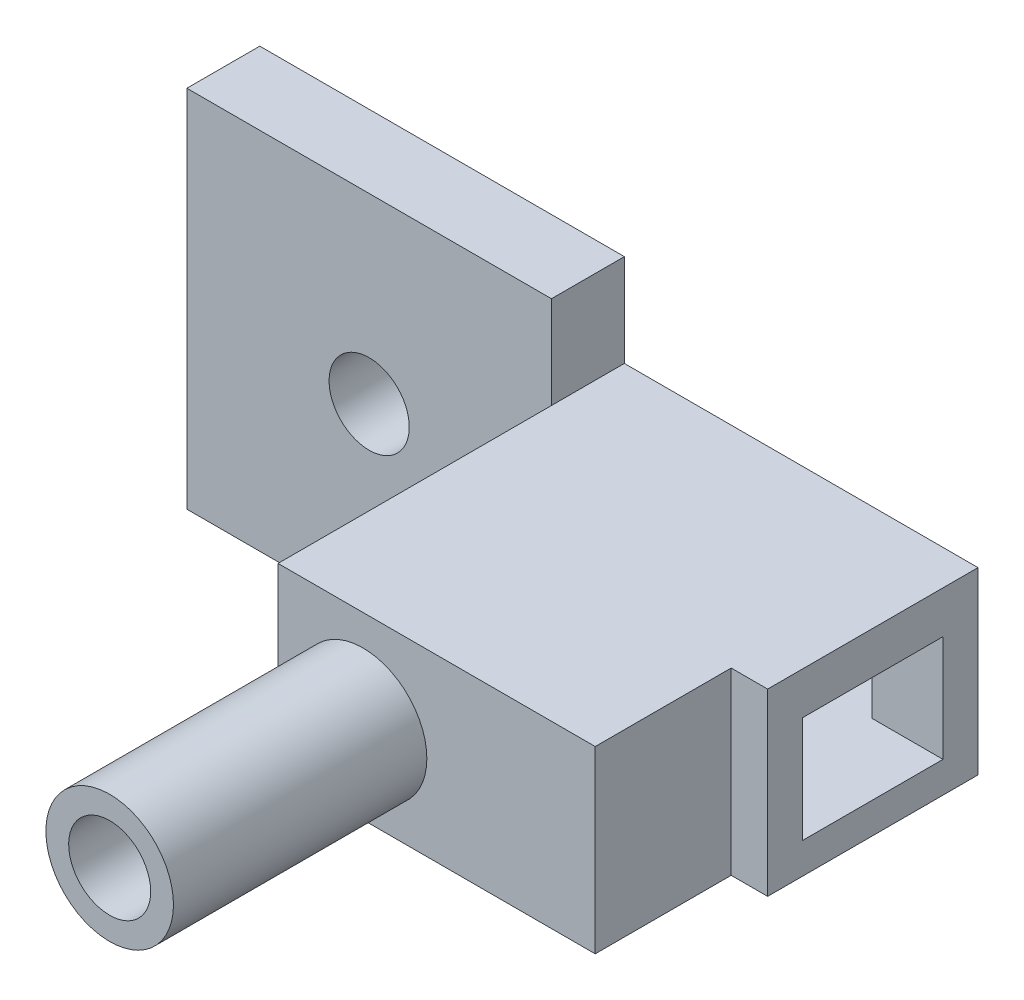
SolidWorks part; units mm, degrees
ref_plane "Front Plane" through (0, 0, 0) normal (0, 0, 1) x (1, 0, 0)
ref_plane "Top Plane" through (0, 0, 0) normal (0, 1, 0) x (1, 0, 0)
ref_plane "Right Plane" through (0, 0, 0) normal (1, 0, 0) x (0, 0, -1)
sketch "Sketch1" plane through (0, 0, 0) normal (0, 0, 1) x (1, 0, 0)
  line L0 (3.92, 6.85) -> (1.72, 6.85) construction
  line L1 (-2, 7.85) -> (15.4, 7.85)
  line L2 (-2, 7.85) -> (-2, -2.0005)
  line L3 (-2, -2.0005) -> (15.4, -2.0005)
  line L4 (15.4, 7.85) -> (15.4, -2.0005)
  line L5 (13.4, 0) -> (0, 0) construction
  line L6 (0, 0) -> (0, 5.33) construction
  line L7 (13.4, 5.33) -> (13.4, 0) construction
  line L8 (0, 4.9339) -> (0, 0.3961)
  line L9 (0.3961, 5.33) -> (4.9339, 5.33)
  line L10 (0, 5.33) -> (13.4, 5.33) construction
  line L11 (0.3961, 0) -> (4.9339, 0)
  circle A0 centre (2.665, 2.665) radius 2.25
  circle A2 centre (2.665, 2.665) radius 3.5
  dimension "D1" = 4.5
  dimension "D2" = 7
  dimension "D3" = 1
  dimension "D4" = 2.0005
  dimension "D5" = 2
  dimension "D6" = 2
extrude "Boss-Extrude1" add sketch "Sketch1" along normal blind 2 contours L8 A2 | L11 A2 | L9 A2 | L4 L1 L2 L3 A2 A0 region at (7.8683, 3, 0) region at (-0.3377, 2.665, 0) region at (2.665, 5.6677, 0) region at (2.665, -0.3377, 0)
extrude "Boss-Extrude2" add sketch "Sketch1<4>" along normal blind 14 from offset 1.9 contours L9 A2 L8 L11 A0 | L8 A2 | L9 A2 | L11 A2 region at (0.2478, 5.0822, 0) region at (-0.3377, 2.665, 0) region at (2.665, 5.6677, 0) region at (2.665, -0.3377, 0)
sketch "Sketch1<4>" plane through (0, 0, 0) normal (0, 0, 1) x (1, 0, 0) same geometry as "Sketch1"
sketch "Sketch2" plane through (0, 0, 0) normal (0, 0, -1) x (-1, 0, 0)
  line L0 (-13.5, 5.53) -> (-11.88, 5.53)
  line L1 (-13.5, -0.3) -> (0.1, -0.3)
  line L2 (-13.5, -0.3) -> (-13.5, 5.53)
  line L4 (0.1, -0.3) -> (0.1, 5.63)
  line L5 (-11.88, 5.53) -> (-11.88, 7.05)
  line L6 (-11.88, 7.05) -> (-9.28, 7.05)
  line L7 (-9.28, 7.05) -> (-9.28, 5.63)
  line L8 (-9.28, 5.63) -> (-4.12, 5.63)
  line L9 (-4.12, 5.63) -> (-4.12, 7.05)
  line L10 (-4.12, 7.05) -> (-1.52, 7.05)
  line L11 (-1.52, 7.05) -> (-1.52, 5.63)
  line L12 (-1.52, 5.63) -> (0.1, 5.63)
  line L13 (-13.4, 5.33) -> (-13.4, 0) construction
  line L15 (-13.4, 0) -> (0, 0) construction
  line L17 (0, 4.9339) -> (0, 0.3961) construction
  line L19 (0, 5.33) -> (-13.4, 5.33) construction
  line L21 (-9.48, 6.85) -> (-11.68, 6.85) construction
  line L22 (-11.68, 6.85) -> (-11.68, 5.33) construction
  line L23 (-1.72, 5.33) -> (-1.72, 6.85) construction
  line L26 (-1.72, 6.85) -> (-3.92, 6.85) construction
  line L27 (-3.92, 6.85) -> (-3.92, 5.33) construction
  line L28 (-9.48, 5.33) -> (-9.48, 6.85) construction
  line L30 (-15.4, 7.85) -> (2, 7.85)
  line L31 (-15.4, 7.85) -> (-15.4, -2.0005)
  line L32 (-15.4, -2.0005) -> (2, -2.0005)
  line L33 (2, 7.85) -> (2, -2.0005)
  dimension "D1" = 0.1
  dimension "D2" = 0.3
  dimension "D3" = 0.1
  dimension "D4" = 0.3
  dimension "D5" = 0.2
  dimension "D6" = 0.2
  dimension "D7" = 0.2
  dimension "D8" = 0.2
  dimension "D9" = 0.2
  dimension "D10" = 0.2
  dimension "D11" = 0.2
extrude "Boss-Extrude3" add sketch "Sketch2" along normal blind 17
sketch "Sketch4" plane through (13.5, 0, 0) normal (-1, 0, 0) x (0, 0, 1)
  line L0 (-17, -0.3) -> (0, -0.3) construction
  line L1 (-15.08, 5.53) -> (-7.38, 5.53)
  line L2 (-15.08, 5.53) -> (-15.08, -0.3)
  line L3 (-15.08, -0.3) -> (-7.38, -0.3)
  line L4 (-7.38, 5.53) -> (-7.38, -0.3)
  line L5 (-17, 5.53) -> (0, 5.53) construction
  line L6 (-6.88, 5.33) -> (-6.88, 0) construction
  dimension "D1" = 7.7
  dimension "D2" = 0.5
extrude "Cut-Extrude1" cut sketch "Sketch4" against normal up to surface (1.9 mm away) up to face at (15.4, 2.9248, -7.5)
sketch "Sketch5" plane through (0, 0, -17) normal (0, 0, -1) x (-1, 0, 0)
  line L0 (2, -2.0005) -> (2, 7.85) construction
  line L1 (2, 12.9248) -> (22, 12.9248)
  line L2 (2, 12.9248) -> (2, -7.0752)
  line L3 (2, -7.0752) -> (22, -7.0752)
  line L4 (22, 12.9248) -> (22, -7.0752)
  line L5 (2, -7.0752) -> (22, 12.9248) construction
  circle A0 centre (12, 2.9248) radius 2.2
  point P6 (2, 2.9248)
  point P7 (2, 2.9248)
  point P11 (12, 2.9248)
  dimension "D3" = 4.4
  dimension "D1" = 20
  dimension "D2" = 20
extrude "Boss-Extrude4" add sketch "Sketch5" against normal blind 4
chamfer "Chamfer1" distance 0.5 angle 45 6 edges at (0.1901, 5.1399, 1.9) (0, 2.665, 1.9) (0.1901, 0.1901, 1.9) (2.665, 0, 1.9) (6.165, 2.665, 1.9) (2.665, 5.33, 1.9)
sketch "Sketch6" plane through (15.4, 0, 0) normal (1, 0, 0) x (0, 0, -1)
  line L0 (-2, -2.0005) -> (17, -2.0005) construction
  line L1 (7.38, -0.3) -> (15.08, -0.3)
  line L2 (7.38, -0.3) -> (7.38, 5.53)
  line L3 (7.38, 5.53) -> (15.08, 5.53)
  line L4 (15.08, -0.3) -> (15.08, 5.53)
  line L5 (5.46, -2.0005) -> (17, -2.0005)
  line L6 (5.46, -2.0005) -> (5.46, 7.85)
  line L7 (5.46, 7.85) -> (17, 7.85)
  line L8 (17, -2.0005) -> (17, 7.85)
  dimension "D1" = 1.92
extrude "Boss-Extrude5" add sketch "Sketch6" along normal blind 2
